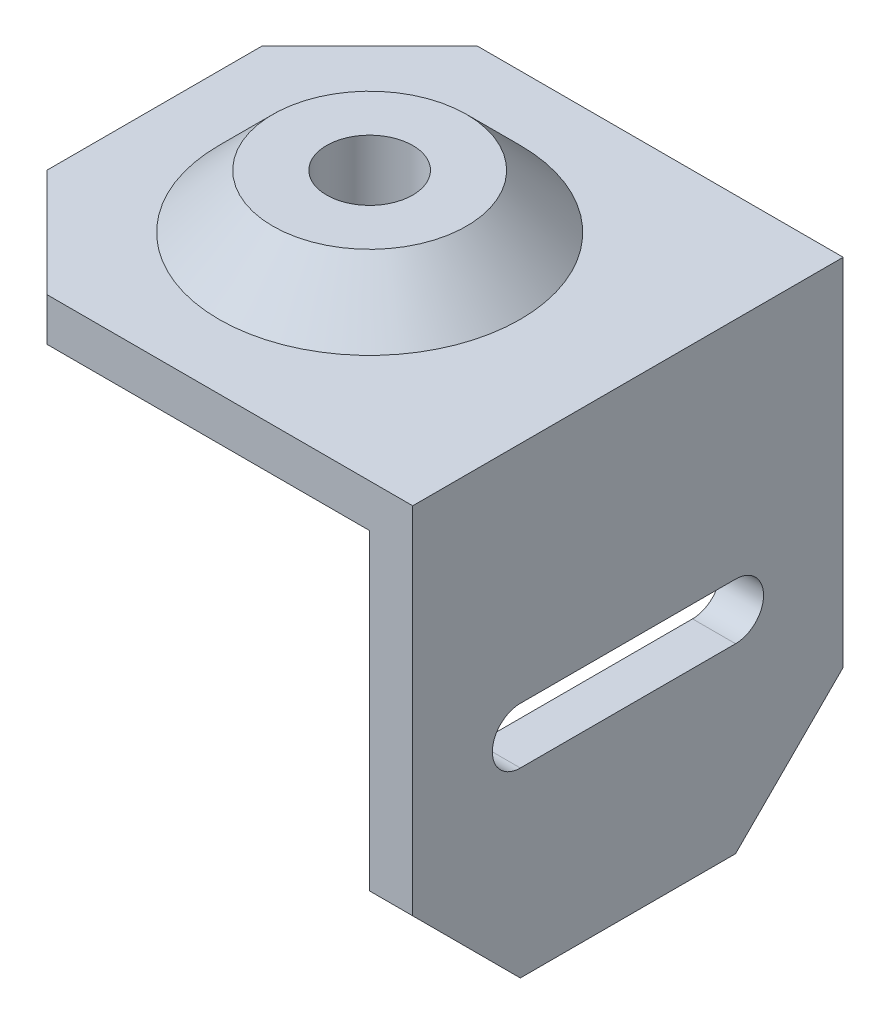
SolidWorks part; units mm, degrees
ref_plane "Front Plane" through (0, 0, 0) normal (0, 0, 1) x (1, 0, 0)
ref_plane "Top Plane" through (0, 0, 0) normal (0, 1, 0) x (1, 0, 0)
ref_plane "Right Plane" through (0, 0, 0) normal (1, 0, 0) x (0, 0, -1)
sketch "Sketch1" plane through (0, 0, 0) normal (0, 1, 0) x (1, 0, 0)
  line L1 (-20, 20) -> (20, 20)
  line L2 (-20, 20) -> (-20, -20)
  line L3 (-20, -20) -> (20, -20)
  line L4 (20, 20) -> (20, -20)
  line L5 (-20, 20) -> (20, -20) construction
  line L6 (-20, -20) -> (20, 20) construction
  circle A0 centre (0, 0) radius 4
  point P0 (0, 0)
  dimension "D3" = 8
  dimension "D1" = 40
  dimension "D2" = 40
extrude "Boss-Extrude1" add sketch "Sketch1" along normal blind 4
sketch "Sketch2" plane through (0, 4, 0) normal (0, 1, 0) x (1, 0, 0)
  circle A0 centre (0, 0) radius 4
  circle A1 centre (0, 0) radius 9
  circle A2 centre (0, 0) radius 4 construction
  dimension "D1" = 5
extrude "Boss-Extrude2" add sketch "Sketch2" along normal blind 5
sketch "Sketch3" plane through (20, 0, 0) normal (1, 0, 0) x (0, 0, -1)
  line L1 (-20, 4) -> (20, 4)
  line L2 (-20, 4) -> (-20, -39)
  line L3 (-20, -39) -> (20, -39)
  line L4 (20, 4) -> (20, -39)
  dimension "D1" = 43
extrude "Boss-Extrude3" add sketch "Sketch3" along normal blind 4
sketch "Sketch4" plane through (20, 0, 0) normal (-1, 0, 0) x (0, 0, 1)
  line L0 (-20, 0) -> (20, -39) construction
  line L1 (-10, -19.5) -> (10, -19.5) construction
  line L2 (-10, -16.9) -> (10, -16.9)
  line L3 (-10, -22.1) -> (10, -22.1)
  arc A0 (-10, -16.9) -> (-10, -22.1) centre (-10, -19.5) ccw
  arc A1 (10, -22.1) -> (10, -16.9) centre (10, -19.5) ccw
  point P6 (0, -19.5)
  dimension "D2" = 2.6
  dimension "D1" = 20
extrude "Cut-Extrude1" cut sketch "Sketch4" against normal through all both and the other way through all
chamfer "Chamfer2" distance 5 angle 45 1 edges at (0, 4, 9)
chamfer "Chamfer3" distance 10 angle 45 4 edges at (22, -39, -20) (22, -39, 20) (-20, 2, -20) (-20, 2, 20)
